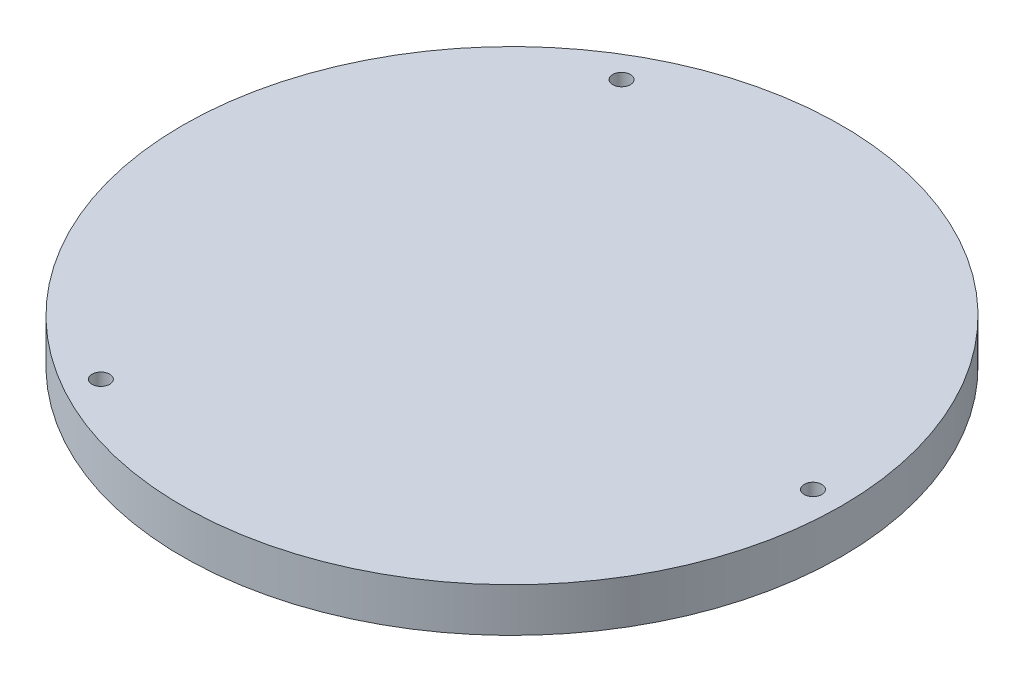
SolidWorks part; units mm, degrees
ref_plane "Front Plane" through (0, 0, 0) normal (0, 0, 1) x (1, 0, 0)
ref_plane "Top Plane" through (0, 0, 0) normal (0, 1, 0) x (1, 0, 0)
ref_plane "Right Plane" through (0, 0, 0) normal (1, 0, 0) x (0, 0, -1)
sketch "Sketch1" plane through (0, 0, 0) normal (0, 0, 1) x (1, 0, 0)
  line L0 (0, -200000) -> (0, 218797.9879) construction
  line L1 (95.25, -26.7494) -> (95.25, -39.4494) construction
  line L2 (0, -26.7494) -> (95.25, -26.7494) construction
  line L3 (95.25, -39.4494) -> (0, -39.4494) construction
  line L4 (0, -200000) -> (0, 218797.9879) construction
  line L5 (95.25, -26.7494) -> (95.25, -39.4494)
  line L6 (0, -26.7494) -> (95.25, -26.7494)
  line L7 (95.25, -39.4494) -> (0, -39.4494)
  line L8 (0, -26.7494) -> (0, -39.4494)
revolve "Revolve1" add sketch "Sketch1" angle 360 about L4
hole_wizard "1/4-20 Tapped Hole1" positions "Sketch2" profile "Sketch3" tap size "1/4-20" standard "ANSI Inch" end condition up to next
sketch "Sketch2" plane through (0, -26.7494, 0) normal (0, 1, 0) x (1, 0, 0)
  line L0 (0, 0) -> (86.995, 0) construction
  line L3 (0, 0) -> (-43.4975, -75.3399) construction
  line L6 (0, 0) -> (-43.2486, 74.9088) construction
  circle A0 centre (0, 0) radius 86.995
  point P0 (86.995, 0)
  point P2 (-43.4975, -75.3399)
  point P4 (-43.2486, 74.9088)
  point P28 (0, 0)
  point P29 (86.311, 0)
  dimension "D1" = 120
  dimension "D2" = 120
sketch "Sketch3" plane through (86.995, -26.7494, 0) normal (1, 0, 0) x (0, 0, 1)
  line L0 (0, 0) -> (0, 12.7)
  line L1 (0, 12.7) -> (2.5527, 12.7)
  line L2 (2.5527, 12.7) -> (2.5527, 0)
  line L5 (2.5527, 0) -> (0, 0)
  line L11 (0, -6.35) -> (0, 107.95) construction
  dimension "Thru Tap Drill Dia." = 5.1054
  dimension "Thru Tap Drill Depth" = 12.7
cosmetic thread "Hole Thread1"
cosmetic thread "Hole Thread2"
cosmetic thread "Hole Thread3"
